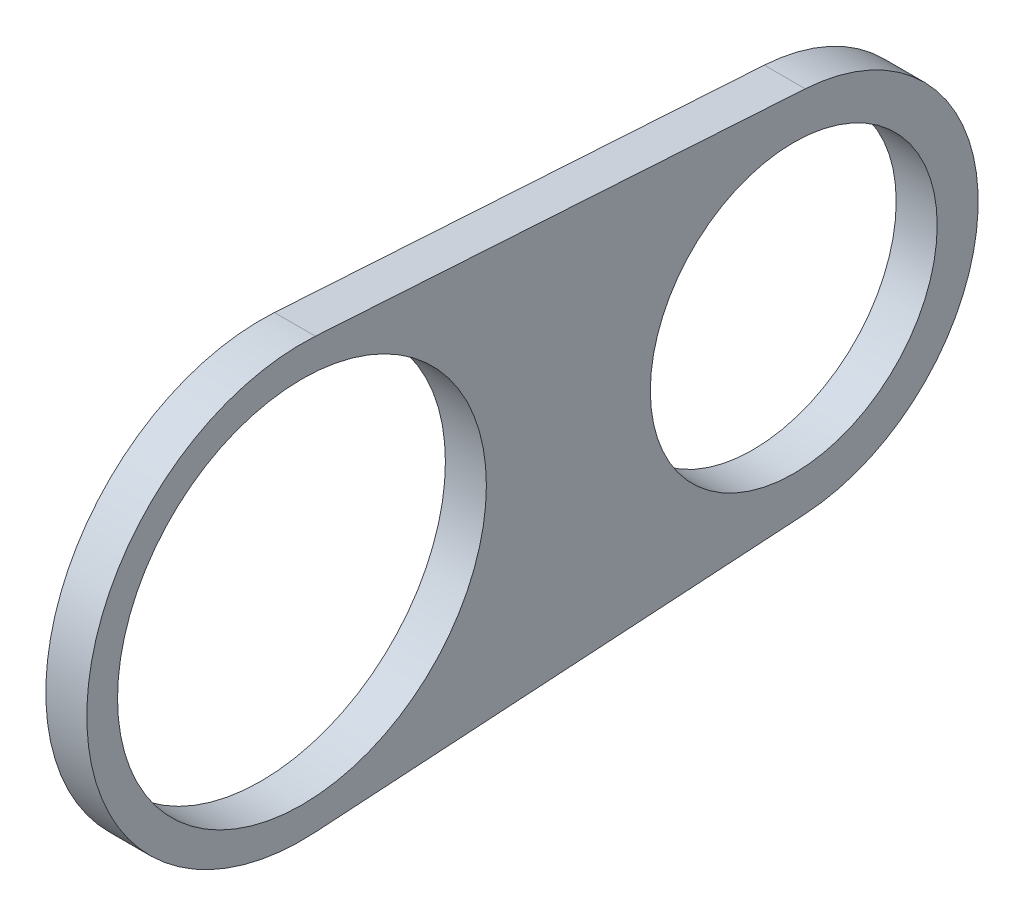
SolidWorks part; units mm, degrees
material "6061-T6 (SS)"
ref_plane "Front" through (0, 0, 0) normal (0, 0, 1) x (1, 0, 0)
ref_plane "Top" through (0, 0, 0) normal (0, 1, 0) x (1, 0, 0)
ref_plane "Right" through (0, 0, 0) normal (1, 0, 0) x (0, 0, -1)
sketch "Sketch1" plane through (0, 0, 0) normal (1, 0, 0) x (0, 0, -1)
  line L0 (-18.0082, 16.6362) -> (19.943, 14.2596)
  line L3 (-18.0082, -16.6362) -> (19.943, -14.2596)
  line L4 (-19.05, 0) -> (19.05, 0) construction
  circle A2 centre (-19.05, 0) radius 14.2875
  circle A3 centre (19.05, 0) radius 11.1125
  arc A4 (19.943, -14.2596) -> (19.943, 14.2596) centre (19.05, 0) ccw
  arc A5 (-18.0082, 16.6362) -> (-18.0082, -16.6362) centre (-19.05, 0) ccw
  point P0 (-15.5478, -16.4388)
  point P13 (0, 0)
  dimension "D1" = 28.575
  dimension "D2" = 2.3812
  dimension "D4" = 22.225
  dimension "D3" = 3.175
  dimension "D5" = 38.1
extrude "Boss-Extrude1" add sketch "Sketch1" along normal blind 3.175
